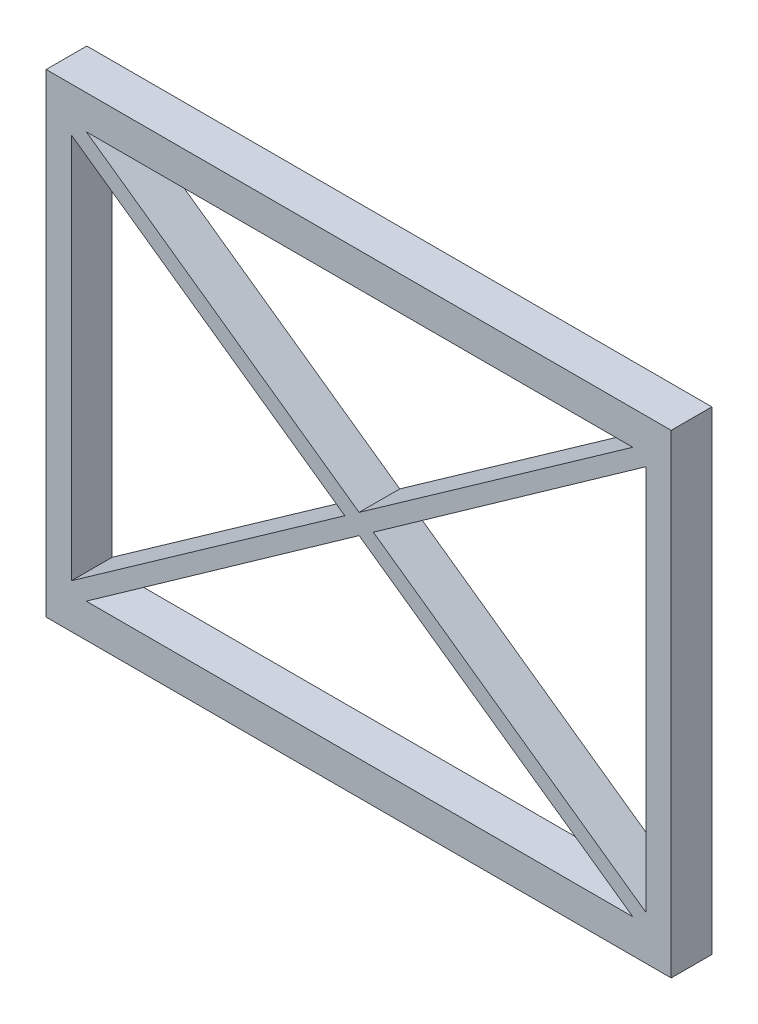
SolidWorks part; units mm, degrees
ref_plane "Front Plane" through (0, 0, 0) normal (0, 0, 1) x (1, 0, 0)
ref_plane "Top Plane" through (0, 0, 0) normal (0, 1, 0) x (1, 0, 0)
ref_plane "Right Plane" through (0, 0, 0) normal (1, 0, 0) x (0, 0, -1)
sketch "Sketch1" plane through (0, 0, 0) normal (0, 1, 0) x (1, 0, 0)
  line L1 (-0.9347, 2.0973) -> (72.8653, 2.0973)
  line L2 (-0.9347, 2.0973) -> (-0.9347, -2.7027)
  line L3 (-0.9347, -2.7027) -> (72.8653, -2.7027)
  line L4 (72.8653, 2.0973) -> (72.8653, -2.7027)
  dimension "D1" = 4.8
  dimension "D2" = 73.8
extrude "Boss-Extrude1" add sketch "Sketch1" along normal blind 56
sketch "Sketch2" plane through (0, 0, 2.7027) normal (0, 0, 1) x (1, 0, 0)
  line L0 (-0.9347, 56) -> (72.8653, 56) construction
  line L1 (2.0653, 52) -> (69.8653, 52)
  line L2 (2.0653, 52) -> (2.0653, 4)
  line L3 (2.0653, 4) -> (69.8653, 4)
  line L4 (69.8653, 52) -> (69.8653, 4)
  line L5 (-0.9347, 0) -> (72.8653, 0) construction
  line L6 (-0.9347, 56) -> (-0.9347, 0) construction
  line L7 (72.8653, 56) -> (72.8653, 0) construction
  line L10 (3.7994, 52) -> (36.0166, 29.1896)
  line L11 (2.0653, 50.776) -> (34.3313, 28)
  line L12 (68.3313, 52) -> (36.0166, 29.1896)
  line L13 (69.8653, 50.776) -> (37.6968, 28)
  line L14 (34.3313, 28) -> (2.0653, 5.224)
  line L16 (36.0166, 26.8104) -> (68.3313, 4)
  line L17 (36.0166, 26.8104) -> (3.7994, 4)
  line L18 (37.6968, 28) -> (69.8653, 5.224)
  dimension "D1" = 4
  dimension "D2" = 4
  dimension "D3" = 3
  dimension "D4" = 3
extrude "Cut-Extrude1" cut sketch "Sketch2" against normal blind 56 contours L12 L1 L10 | L14 L11 L2 | L16 L17 L3 | L13 L18 L4 region at (36.0491, 44.3965, 2.7027) region at (12.8206, 28, 2.7027) region at (59.1425, 28, 2.7027) region at (36.0491, 11.6035, 2.7027)
